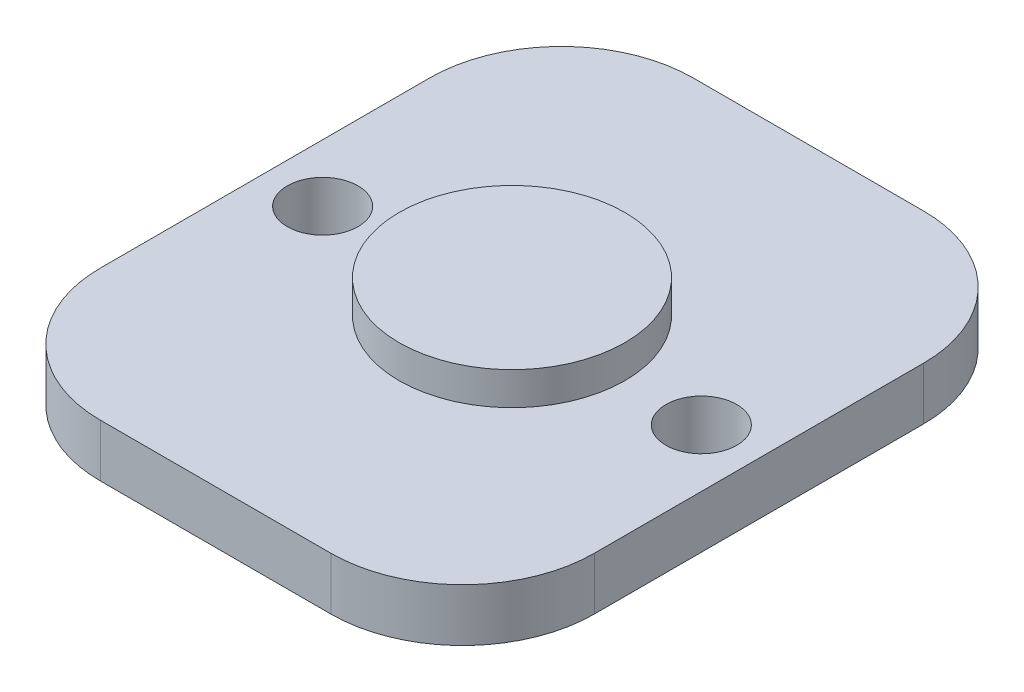
SolidWorks part; units mm, degrees
ref_plane "Front Plane" through (0, 0, 0) normal (0, 0, 1) x (1, 0, 0)
ref_plane "Top Plane" through (0, 0, 0) normal (0, 1, 0) x (1, 0, 0)
ref_plane "Right Plane" through (0, 0, 0) normal (1, 0, 0) x (0, 0, -1)
sketch "Sketch1" plane through (0, 0, 0) normal (0, 1, 0) x (1, 0, 0)
  line L0 (-3.5, 9) -> (3.5, 9)
  line L1 (7.5, 5) -> (7.5, -5)
  line L2 (3.5, -9) -> (-3.5, -9)
  line L3 (-7.5, -5) -> (-7.5, 5)
  line L4 (-7.5, 9) -> (7.5, -9) construction
  line L5 (-5.75, 0) -> (5.75, 0) construction
  arc A0 (-3.5, -9) -> (-7.5, -5) centre (-3.5, -5) cw
  arc A1 (7.5, -5) -> (3.5, -9) centre (3.5, -5) cw
  arc A2 (7.5, 5) -> (3.5, 9) centre (3.5, 5) ccw
  arc A3 (-3.5, 9) -> (-7.5, 5) centre (-3.5, 5) ccw
  circle A4 centre (-5.75, 0) radius 1.075
  circle A5 centre (5.75, 0) radius 1.075
  point P12 (7.5, 9)
  dimension "D3" = 4
  dimension "D4" = 2.15
  dimension "D1" = 15
  dimension "D2" = 18
  dimension "D5" = 11.5
extrude "Boss-Extrude1" add sketch "Sketch1" along normal blind 1.6
sketch "Sketch2" plane through (0, 1.6, 0) normal (0, 1, 0) x (1, 0, 0)
  circle A0 centre (0, 0) radius 3.4265
extrude "Boss-Extrude2" add sketch "Sketch2" along normal blind 1
